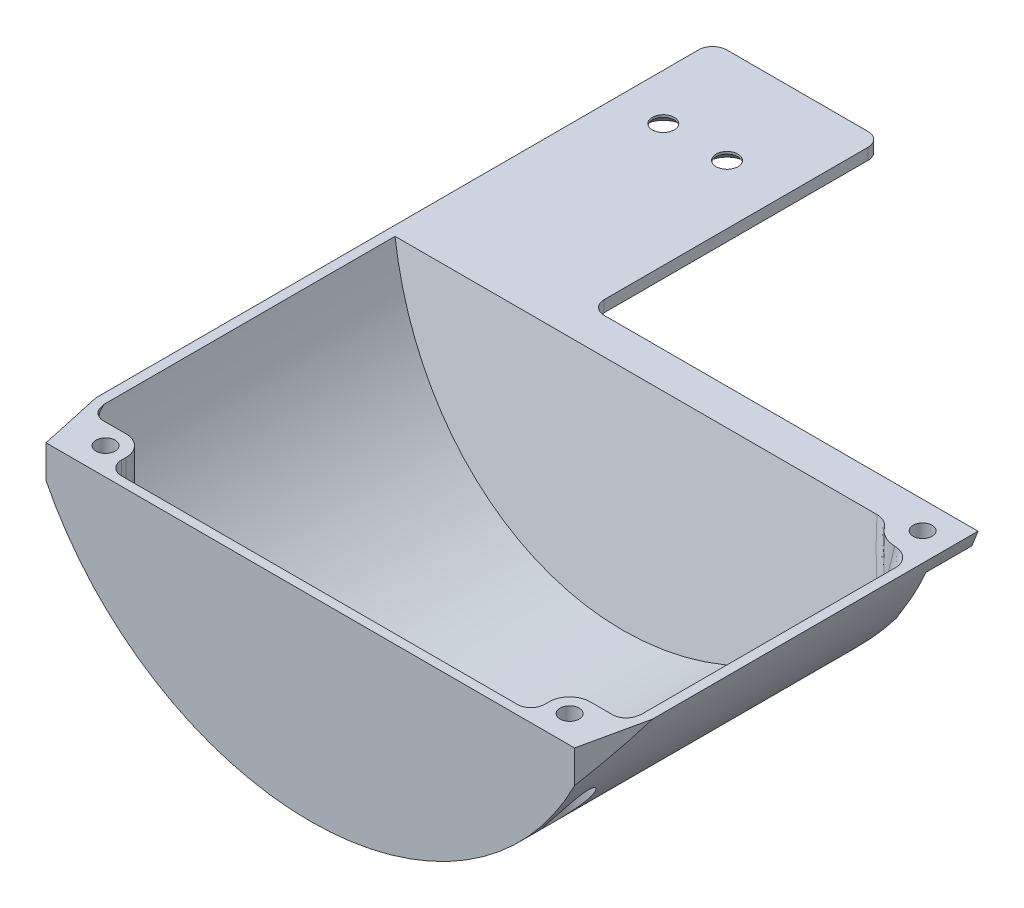
SolidWorks part; units mm, degrees
material "7050-T7451"
ref_plane "前视基准面" through (0, 0, 0) normal (0, 0, 1) x (1, 0, 0)
ref_plane "上视基准面" through (0, 0, 0) normal (0, 1, 0) x (1, 0, 0)
ref_plane "右视基准面" through (0, 0, 0) normal (1, 0, 0) x (0, 0, -1)
sketch "草图1" plane through (0, 0, 0) normal (0, 0, 1) x (1, 0, 0)
  circle A0 centre (0, 0) radius 32.5
  dimension "D1" = 65
extrude "凸台-拉伸1" add sketch "草图1" along normal blind 150
sketch "草图2" plane through (0, 0, 150) normal (0, 0, 1) x (1, 0, 0)
  line L1 (-33.541, 10) -> (33.541, 10)
  arc A1 (33.541, 10) -> (-33.541, 10) centre (0, 0) ccw
  dimension "D3" = 35
  dimension "D2" = 10
extrude "切除-拉伸1" cut sketch "草图2" against normal blind 50
sketch "草图3" plane through (0, 10, 0) normal (0, 1, 0) x (1, 0, 0)
  line L0 (0, 0) -> (0, -94.1465) construction
  line L1 (-30.9233, -150) -> (30.9233, -150) construction
  circle A0 centre (0, -117) radius 5
  dimension "D1" = 33
  dimension "D2" = 10
extrude "切除-拉伸2" cut sketch "草图3" against normal blind 3
sketch "草图5" plane through (0, 10, 0) normal (0, 1, 0) x (1, 0, 0)
  line L0 (-26.7844, -111.1263) -> (-23, -111.1263)
  line L1 (-79.9728, -85) -> (-79.9728, -232.1559)
  line L2 (-79.9728, -232.1559) -> (70.7914, -232.1559)
  line L3 (70.7914, -232.1559) -> (70.7914, -85)
  line L4 (-26.7844, -111.1263) -> (-32.5, -85)
  line L5 (-23, -111.1263) -> (-23, -117)
  line L6 (0, -117) -> (0, -155.754) construction
  line L7 (23, -117) -> (23, -111.1263)
  line L8 (26.7844, -111.1263) -> (32.5, -85)
  line L9 (-79.9728, -85) -> (-32.5, -85)
  line L10 (32.5, -85) -> (70.7914, -85)
  line L11 (23, -111.1263) -> (26.7844, -111.1263)
  arc A0 (-23, -117) -> (23, -117) centre (0, -117) ccw
  dimension "D3" = 23
  dimension "D1" = 32
  dimension "D2" = 102.34
  dimension "D4" = 65
extrude "切除-拉伸4" cut sketch "草图5" against normal mid plane 100 contours L1 L2 L3 L10 L8 L11 L7 A0 L5 L0 L4 L9
sketch "草图7" plane through (0, 0, 0) normal (0, 0, -1) x (-1, 0, 0)
  line L1 (-40, 55.352) -> (39.3788, 55.352)
  line L2 (-40, 55.352) -> (-40, -48.8167)
  line L3 (-40, -48.8167) -> (39.3788, -48.8167)
  line L4 (39.3788, 55.352) -> (39.3788, -48.8167)
  dimension "D2" = 40
extrude "切除-拉伸5" cut sketch "草图7" against normal blind 58
ref_plane "基准面2" through (0, 0, 100) normal (0, 0, -1) x (-1, 0, 0)
sketch "草图10" plane through (0, 0, 100) normal (0, 0, -1) x (-1, 0, 0)
  line L5 (-40.1828, -50) -> (43.1948, -50)
  line L6 (-40.1828, -50) -> (-40.1828, 42.487)
  line L7 (-40.1828, 42.487) -> (43.1948, 42.487)
  line L8 (43.1948, -50) -> (43.1948, 42.487)
  dimension "D1" = 50
extrude "切除-拉伸9" cut sketch "草图10" against normal through all
sketch "草图11" plane through (0, 0, 100) normal (0, 0, -1) x (-1, 0, 0)
  line L1 (-57.2383, 47.9039) -> (49.9155, 47.9039)
  line L2 (-57.2383, 47.9039) -> (-57.2383, -11)
  line L3 (-57.2383, -11) -> (49.9155, -11)
  line L4 (49.9155, 47.9039) -> (49.9155, -11)
  dimension "D1" = 11
extrude "切除-拉伸10" cut sketch "草图11" along normal through all
sketch "草图24" plane through (0, 0, 0) normal (1, 0, 0) x (0, 0, -1)
  line L0 (-61.6, -14) -> (-61.2172, -12.25)
  line L1 (-58, -32.5) -> (-58, -11) construction
  line L2 (-93.768, -11) -> (-58, -11) construction
  line L3 (-61.2172, -12.25) -> (-56.3867, -12.25)
  line L7 (-50.3058, -35.9412) -> (-56.3867, -12.25)
  line L8 (-66.4012, -35.9465) -> (-50.3058, -35.9412)
  line L9 (-61.6, -14) -> (-66.4012, -35.9465)
  line L12 (-58, -11) -> (-53.3731, -11) construction
  dimension "D1" = 3
  dimension "D3" = 3.6
  dimension "D4" = 102.34
  dimension "D5" = 1.25
extrude "切除-拉伸12" cut sketch "草图24" against normal mid plane 80
shell "抽壳1" thickness 1 removed face at (0, -11, 83.9227)
sketch "草图19" plane through (0, -11, 0) normal (0, 1, 0) x (1, 0, 0)
  line L0 (29.5169, -93.9566) -> (29.5169, -59) construction
  line L1 (-29.5169, -59) -> (29.5169, -59)
  line L2 (-29.5169, -59) -> (-29.5169, -59.25)
  line L3 (-29.5169, -59.25) -> (29.5169, -59.25)
  line L4 (29.5169, -59) -> (29.5169, -59.25)
  dimension "D1" = 0.25
extrude "凸台-拉伸5" add sketch "草图19" against normal up to next
sketch "草图16" plane through (0, -11, 0) normal (0, 1, 0) x (1, 0, 0)
  line L0 (-12, -59.25) -> (-30.5819, -59.25)
  line L1 (30.5819, -58) -> (-30.5819, -58) construction
  line L2 (-29.5169, -59.25) -> (29.5169, -59.25) construction
  line L3 (-12, -59.25) -> (-12, -26)
  line L4 (-12, -26) -> (-30.5819, -26)
  line L5 (-30.5819, -59.25) -> (-30.5819, -26)
  line L7 (-30.5819, -58) -> (-30.5819, -93.768) construction
  dimension "D1" = 32
  dimension "D2" = 12
  dimension "D4" = 0
extrude "凸台-拉伸4" add sketch "草图16" against normal blind 1.25
sketch "草图20" plane through (0, -11, 0) normal (0, 1, 0) x (1, 0, 0)
  line L0 (-12, -58) -> (30.5819, -58) construction
  line L2 (0, 0) -> (0, -129.4933) construction
  line L3 (24.5, -61) -> (24.5, -58)
  line L10 (-12, -58) -> (30.5819, -58) construction
  line L11 (24.5, -58) -> (30.5, -58)
  line L12 (30.5, -58) -> (30.5, -61)
  arc A2 (24.5, -61) -> (30.5, -61) centre (27.5, -61) ccw
  dimension "D3" = 3
  dimension "D6" = 6
  dimension "D4" = 27.5
  dimension "D7" = 0
extrude "凸台-拉伸6" add sketch "草图20" against normal up to next
sketch "草图32" plane through (0, -11, 0) normal (0, 1, 0) x (1, 0, 0)
  line L0 (0, -98.5) -> (0, 1.4961) construction
  line L2 (29.2185, -100) -> (-29.2185, -100) construction
  line L3 (23.25, -97.8) -> (23.25, -100)
  line L4 (23.25, -100) -> (27.75, -100)
  line L5 (27.75, -100) -> (27.75, -97.8)
  line L6 (-23.25, -97.8) -> (-23.25, -100)
  line L7 (-23.25, -100) -> (-27.75, -100)
  line L8 (-27.75, -100) -> (-27.75, -97.8)
  arc A0 (27.75, -97.8) -> (23.25, -97.8) centre (25.5, -97.8) ccw
  arc A1 (-27.75, -97.8) -> (-23.25, -97.8) centre (-25.5, -97.8) cw
  dimension "D3" = 4.5
  dimension "D1" = 51
  dimension "D2" = 2.2
extrude "凸台-拉伸8" add sketch "草图32" against normal up to next
hole_wizard "Ø2.1 (2.1) 直径孔1" positions "草图22" profile "草图21" hole size "Ø2.1" standard "GB" end condition through all
sketch "草图22" plane through (0, -11, 0) normal (0, 1, 0) x (1, 0, 0)
  point P6 (-25.5, -97.8)
  point P12 (27.5, -61)
  point P19 (25.5, -97.8)
sketch "草图21" plane through (-25.5, -11, 97.8) normal (1, 0, 0) x (0, 0, 1)
  line L0 (0, 0) -> (0, 21.5)
  line L1 (0, 21.5) -> (1.05, 21.5)
  line L2 (1.05, 21.5) -> (1.05, 0)
  line L5 (1.05, 0) -> (0, 0)
  line L11 (0, -6.35) -> (0, 107.95) construction
  dimension "通孔孔直径" = 2.1
  dimension "通孔孔深度" = 21.5
ref_plane "基准面3" through (0, -17, 0) normal (0, 1, 0) x (1, 0, 0)
sketch "草图23" plane through (0, -17, 0) normal (0, 1, 0) x (1, 0, 0)
  circle A1 centre (25.5, -97.8) radius 2.05
  circle A2 centre (-25.5, -97.8) radius 2.05
  dimension "D1" = 4.1
  dimension "D2" = 4.1
extrude "切除-拉伸11" cut sketch "草图23" against normal blind 11
sketch "草图25" plane through (0, 0, 59.25) normal (0, 0, 1) x (1, 0, 0)
  line L0 (-32.5, 0) -> (-35.6283, 0)
  line L1 (-35.6283, 0) -> (-35.6283, -32.5)
  line L2 (-35.6283, -32.5) -> (-29.7867, -32.5)
  line L3 (-29.7867, -32.5) -> (-29.7867, -13)
  arc A0 (-32.5, 0) -> (-29.7867, -13) centre (0, 0) ccw
extrude "切除-拉伸13" cut sketch "草图25" against normal through all
sketch "草图31" plane through (0, 0, 58) normal (0, 0, -1) x (-1, 0, 0)
  line L0 (-27.7924, -16.8473) -> (-34.5324, -16.8473)
  line L1 (-34.5324, -16.8473) -> (-34.5324, -7.3294)
  line L2 (-34.5324, -7.3294) -> (-31.6627, -7.3294)
  arc A0 (-31.6627, -7.3294) -> (-27.7924, -16.8473) centre (0, 0) ccw
  dimension "D1" = 65
  dimension "D2" = 5.8473
fillet "圆角1" radius 1.5 3 edges at (-12, -11.625, 58) (-12, -11.625, 26) (-30.3488, -11.6275, 26)
ref_axis "基准轴1" through (27.5, -16.057, 61) along (0, 1, 0)
sketch "草图39" plane through (0, -11, 0) normal (0, 1, 0) x (1, 0, 0)
  line L0 (-23.25, -99) -> (-23.25, -97.8) construction
  line L1 (-23.25, -98.4) -> (23.25, -98.4)
  line L2 (-23.25, -98.4) -> (-23.25, -99.8)
  line L3 (-23.25, -99.8) -> (23.25, -99.8)
  line L4 (23.25, -98.4) -> (23.25, -99.8)
  line L5 (23.25, -99) -> (-23.25, -99) construction
  line L6 (23.25, -99) -> (23.25, -97.8) construction
  dimension "D1" = 0.8
extrude "切除-拉伸16" cut sketch "草图39" against normal up to surface (10.2529 mm away) up to face at (-2.0555, -16.7642, 87.0521)
sketch "草图40" plane through (0, -11, 0) normal (0, 1, 0) x (1, 0, 0)
  line L0 (-30.5819, -93.768) -> (-29.2185, -100) construction
  line L1 (30.5819, -93.768) -> (29.2185, -100) construction
  line L2 (-30.5819, -93.768) -> (-29.2185, -100) construction
  line L3 (30.5819, -93.768) -> (29.2185, -100) construction
  line L4 (-29.2185, -100) -> (-29.0435, -100.8)
  line L5 (29.2185, -100) -> (29.0435, -100.8)
  line L6 (-29.0435, -100.8) -> (29.0435, -100.8)
  line L7 (29.2185, -100) -> (-29.2185, -100) construction
  line L8 (-29.2185, -100) -> (29.2185, -100)
  dimension "D1" = 0.8
extrude "凸台-拉伸13" add sketch "草图40" against normal up to surface (3.2313 mm away) up to face at (-25.8422, -19.7086, 95.7788)
sketch "Sketch1" plane through (0, -11, 0) normal (0, 1, 0) x (1, 0, 0)
  line L0 (25.5, -95.55) -> (29.1684, -95.55)
  line L1 (29.5169, -93.9566) -> (28.4136, -99) construction
  line L2 (29.1684, -95.55) -> (28.4136, -99)
  line L3 (28.4136, -99) -> (27.75, -99)
  line L4 (27.75, -99) -> (27.75, -97.8)
  line L5 (-25.5, -95.55) -> (-29.1684, -95.55)
  line L6 (-29.5169, -93.9566) -> (-28.4136, -99) construction
  line L7 (-29.1684, -95.55) -> (-28.4136, -99)
  line L8 (-28.4136, -99) -> (-27.75, -99)
  line L9 (-27.75, -99) -> (-27.75, -97.8)
  arc A0 (27.75, -97.8) -> (23.25, -97.8) centre (25.5, -97.8) ccw construction
  arc A1 (27.75, -97.8) -> (23.25, -97.8) centre (25.5, -97.8) ccw construction
  arc A2 (27.75, -97.8) -> (25.5, -95.55) centre (25.5, -97.8) ccw
  arc A3 (27.75, -97.8) -> (25.5, -95.55) centre (25.5, -97.8) ccw
  arc A4 (-23.25, -97.8) -> (-27.75, -97.8) centre (-25.5, -97.8) ccw construction
  arc A5 (-25.5, -95.55) -> (-27.75, -97.8) centre (-25.5, -97.8) ccw
  arc M3 (-23.25, -97.8) -> (-27.75, -97.8) centre (-25.5, -97.8) ccw
  line M4 (-27.75, -97.8) -> (-27.75, -99)
  line M5 (-27.75, -99) -> (-28.4136, -99)
  line M6 (-28.4136, -99) -> (-29.5169, -93.9566)
  line M12 (29.5169, -93.9566) -> (28.4136, -99)
  line M13 (28.4136, -99) -> (27.75, -99)
  line M14 (27.75, -99) -> (27.75, -97.8)
  arc M15 (27.75, -97.8) -> (23.25, -97.8) centre (25.5, -97.8) ccw
extrude "Boss-Extrude1" add sketch "Sketch1" against normal up to surface (0.8936 mm away) contours L0 M15 M14 M13 M12 | L5 M3 M6 M5 M4 region at (28.0504, -11, 96.8311) region at (-28.0504, -11, 96.8311)
sketch "草图42" plane through (0, -11, 0) normal (0, 1, 0) x (1, 0, 0)
  line L1 (-29.5169, -59.25) -> (24.5022, -59.25)
  line L2 (-29.5169, -59.25) -> (-29.5169, -61.115)
  line L3 (-29.5169, -61.115) -> (24.5022, -61.115)
  line L4 (24.5022, -59.25) -> (24.5022, -61.115)
  arc A0 (24.5, -61) -> (24.6795, -62.022) centre (27.5, -61) ccw construction
  arc A1 (24.5, -61) -> (29.5169, -63.2208) centre (27.5, -61) ccw construction
extrude "凸台-拉伸14" add sketch "草图42" against normal up to next
fillet "Fillet2" radius 1.5 2 edges at (-23.25, -16.1265, 99.8) (23.25, -16.1265, 99.8)
fillet "Fillet4" radius 1.5 1 edges at (-29.1684, -11.4468, 95.55)
fillet "Fillet5" radius 1.5 1 edges at (29.1684, -11.4468, 95.55)
sketch "草图46" plane through (0, 0, 0) normal (1, 0, 0) x (0, 0, -1)
  line L0 (-62.022, -11.25) -> (-61.115, -11.25)
  line L1 (-61.115, -11.25) -> (-62.022, -11.25) construction
  line L2 (-61.115, -11.25) -> (-61.115, -11)
  line L5 (-62.022, -11.25) -> (-61.9673, -11)
  line L6 (-93.768, -11) -> (-58, -11) construction
  line L7 (-61.9673, -11) -> (-61.115, -11)
extrude "凸台-拉伸16" add sketch "草图46" against normal up to body and the other way up to body separate body
sketch "草图47" plane through (0, -11, 0) normal (0, 1, 0) x (1, 0, 0)
  line L0 (-29.0435, -100.8) -> (29.0435, -100.8) construction
  line L1 (-30.5819, -27.5) -> (-30.5819, -93.768) construction
  circle A0 centre (-25.5012, -36.5) radius 1.2
  circle A1 centre (-18.5012, -36.5) radius 1.2
  dimension "D1" = 64.3
  dimension "D2" = 64.3
  dimension "D3" = 7
  dimension "D4" = 2.4
  dimension "D5" = 2.4
  dimension "D6" = 5.0807
extrude "切除-拉伸17" cut sketch "草图47" against normal blind 10
chamfer "倒角1" distance 1 angle 45 2 edges at (-25.5012, -12.25, 37.7) (-18.5012, -12.25, 37.7)
sketch "草图48" plane through (0, -12.25, 0) normal (0, -1, 0) x (1, 0, 0)
  circle A0 centre (27.5, 61) radius 2.05
  dimension "D1" = 4.1
extrude "切除-拉伸19" cut sketch "草图48" along normal blind 9
sketch "草图49" plane through (0, -12.25, 0) normal (0, -1, 0) x (1, 0, 0)
  line L1 (30.1029, 58) -> (27.5, 58)
  line L2 (30.1029, 58) -> (30.1029, 63.05)
  line L3 (30.1029, 63.05) -> (27.5, 63.05)
  line L4 (27.5, 58) -> (27.5, 63.05)
  arc A0 (29.5385, 61.2172) -> (25.4615, 61.2172) centre (27.5, 61) ccw construction
extrude "切除-拉伸20" cut sketch "草图49" along normal blind 8
fillet "圆角2" radius 2 2 edges at (27.3911, -15.5557, 63.998) (25.1246, -14.9537, 62.8323)
sketch "草图50" plane through (0, -12.25, 0) normal (0, -1, 0) x (1, 0, 0)
  line L0 (27.5, 63.05) -> (30.1029, 63.05) construction
  line L1 (27.5, 63.05) -> (30.1029, 63.05)
  line L2 (30.1029, 63.05) -> (30.1029, 58) construction
  line L3 (30.1029, 63.05) -> (30.1029, 58)
  line L4 (30.1029, 58) -> (25.4615, 58)
  line L6 (25.4615, 61.2172) -> (25.4615, 58)
  arc A0 (27.5, 63.05) -> (25.4615, 61.2172) centre (27.5, 61) ccw construction
  arc A1 (27.5, 63.05) -> (25.4615, 61.2172) centre (27.5, 61) ccw
  circle A2 centre (27.5, 61) radius 1.05 construction
  circle A3 centre (27.5, 61) radius 1.05
extrude "凸台-拉伸17" add sketch "草图50" along normal blind 0.5
sketch "草图51" plane through (0, 0, 100.8) normal (0, 0, 1) x (1, 0, 0)
  circle A0 centre (0, 0) radius 32.5
  circle A1 centre (0, 0) radius 35.8152
extrude "切除-拉伸21" cut sketch "草图51" against normal blind 78.5
